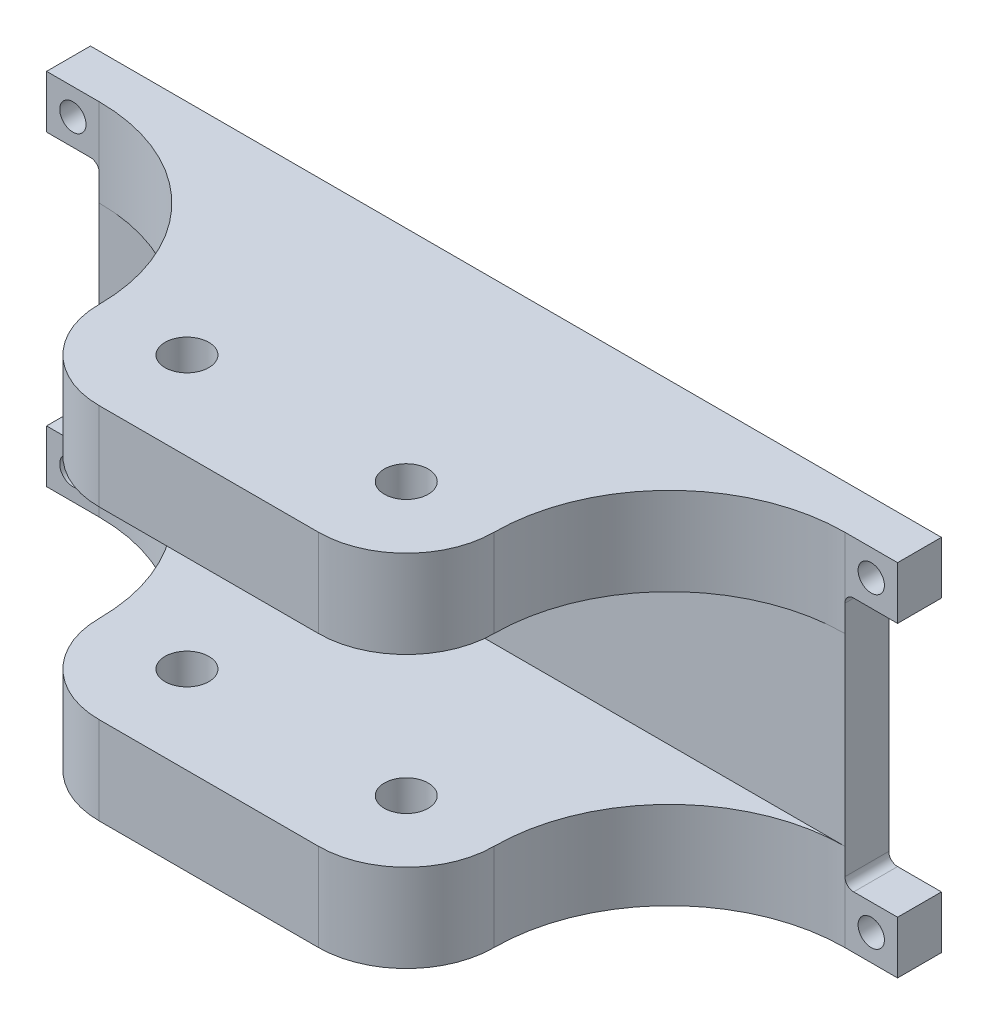
SolidWorks part; units mm, degrees
ref_plane "Front Plane" through (0, 0, 0) normal (0, 0, 1) x (1, 0, 0)
ref_plane "Top Plane" through (0, 0, 0) normal (0, 1, 0) x (1, 0, 0)
ref_plane "Right Plane" through (0, 0, 0) normal (1, 0, 0) x (0, 0, -1)
sketch "Sketch1" plane through (0, 0, 0) normal (0, 0, 1) x (1, 0, 0)
  line L1 (0, 0) -> (85, 0)
  line L2 (0, 0) -> (0, 41)
  line L3 (0, 41) -> (85, 41)
  line L4 (85, 0) -> (85, 41)
  dimension "D1" = 85
  dimension "D2" = 41
extrude "Boss-Extrude1" add sketch "Sketch1" along normal blind 5
sketch "Sketch3" plane through (0, 0, 5) normal (0, 0, 1) x (1, 0, 0)
  line L0 (85, 41) -> (0, 41) construction
  line L1 (20, 41) -> (65, 41)
  line L2 (20, 41) -> (20, 31)
  line L3 (20, 31) -> (65, 31)
  line L4 (65, 41) -> (65, 31)
  line L5 (85, 0) -> (85, 41) construction
  line L6 (0, 0) -> (85, 0) construction
  line L7 (20, 0) -> (65, 0)
  line L8 (20, 0) -> (20, 10)
  line L9 (20, 10) -> (65, 10)
  line L10 (65, 0) -> (65, 10)
  dimension "D1" = 10
  dimension "D2" = 45
  dimension "D3" = 20
  dimension "D4" = 45
  dimension "D5" = 10
extrude "Boss-Extrude3" add sketch "Sketch3" along normal blind 30
sketch "Sketch4" plane through (0, 0, 5) normal (0, 0, 1) x (1, 0, 0)
  line L0 (0, 41) -> (0, 0) construction
  line L1 (-6, 41) -> (0, 41)
  line L2 (-6, 41) -> (-6, 35)
  line L3 (-6, 35) -> (0, 35)
  line L4 (0, 41) -> (0, 35)
  line L5 (20, 41) -> (0, 41) construction
  circle A0 centre (-3, 38) radius 1.5
  dimension "D3" = 3
  dimension "D4" = 3
  dimension "D5" = 3
  dimension "D1" = 6
  dimension "D2" = 6
extrude "Boss-Extrude4" add sketch "Sketch4" against normal blind 5
pattern_linear "LPattern1" count 2 spacing 35 along (0, -1, 0) count 2 spacing 91 along (1, 0, 0) of "Boss-Extrude4"
fillet "Fillet1" radius 20 4 edges at (65, 5, 5) (65, 36, 5) (20, 5, 5) (20, 36, 5)
sketch "Sketch5" plane through (0, 41, 0) normal (0, 1, 0) x (1, 0, 0)
  line L0 (20, -35) -> (20, -25) construction
  line L1 (65, -35) -> (20, -35) construction
  line L2 (65, -35) -> (65, -25) construction
  circle A0 centre (30, -25) radius 2.5
  circle A1 centre (55, -25) radius 2.5
  dimension "D1" = 5
  dimension "D2" = 10
  dimension "D3" = 10
  dimension "D4" = 5
  dimension "D6" = 10
  dimension "D5" = 10
extrude "Cut-Extrude1" cut sketch "Sketch5" against normal blind 41
fillet "Fillet2" radius 1 4 edges at (85, 6, 2.5) (85, 35, 2.5) (0, 35, 2.5) (0, 6, 2.5)
fillet "Fillet3" radius 10 4 edges at (65, 5, 35) (20, 5, 35) (65, 36, 35) (20, 36, 35)
